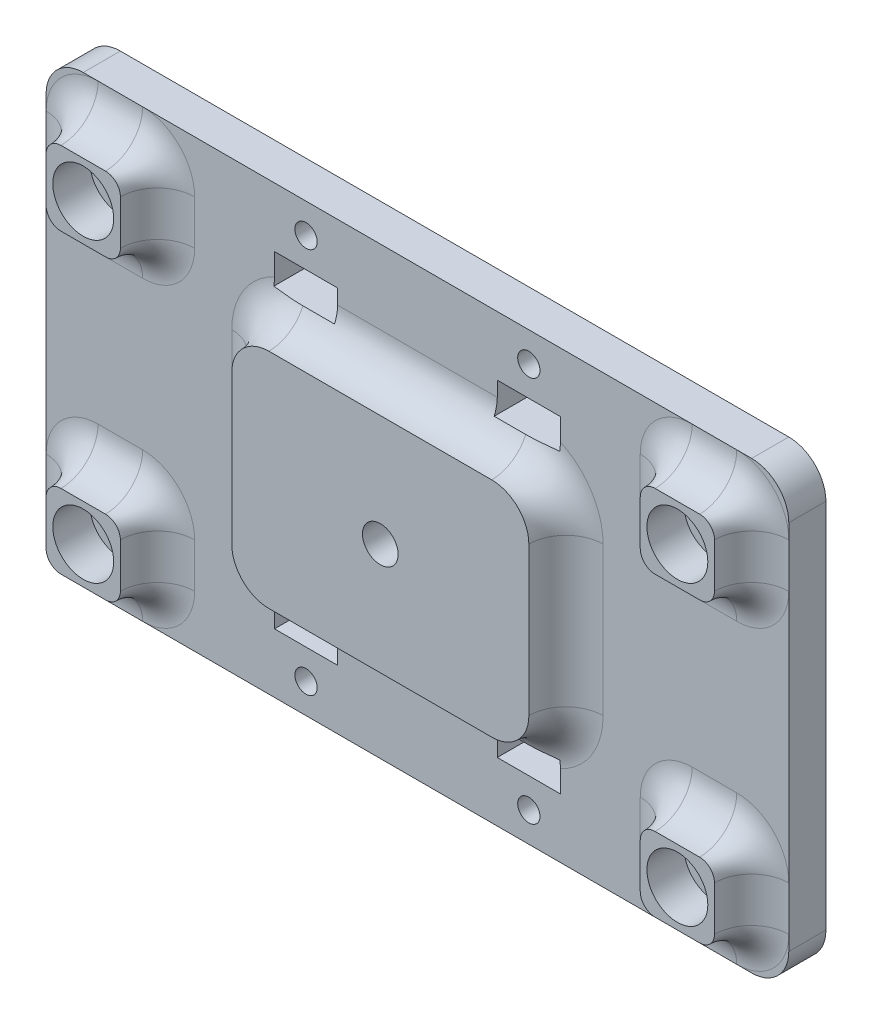
SolidWorks part; units mm, degrees
ref_plane "Front Plane" through (0, 0, 0) normal (0, 0, 1) x (1, 0, 0)
ref_plane "Top Plane" through (0, 0, 0) normal (0, 1, 0) x (1, 0, 0)
ref_plane "Right Plane" through (0, 0, 0) normal (1, 0, 0) x (0, 0, -1)
sketch "Sketch1" plane through (0, 0, 0) normal (0, 0, 1) x (1, 0, 0)
  line L1 (-45, -30) -> (45, -30)
  line L2 (-50, -25) -> (-50, 25)
  line L3 (-45, 30) -> (45, 30)
  line L4 (50, -25) -> (50, 25)
  circle A0 centre (-40, 20) radius 2.25
  circle A1 centre (40, 20) radius 2.25
  circle A2 centre (40, -20) radius 2.25
  circle A3 centre (-40, -20) radius 2.25
  circle A4 centre (0, 0) radius 5
  arc A5 (50, 25) -> (45, 30) centre (45, 25) ccw
  arc A6 (50, -25) -> (45, -30) centre (45, -25) cw
  arc A7 (-45, -30) -> (-50, -25) centre (-45, -25) cw
  arc A8 (-50, 25) -> (-45, 30) centre (-45, 25) cw
  point P0 (0, 0)
  point P6 (0, 0)
  dimension "D1" = 5
  dimension "D3" = 80
  dimension "D4" = 40
extrude "Boss-Extrude1" add sketch "Sketch1" along normal blind 5
sketch "Sketch2" plane through (0, 0, 5) normal (0, 0, 1) x (1, 0, 0)
  line L5 (10.75, -18) -> (19.25, -18)
  line L6 (10.75, -22) -> (10.75, -18)
  line L7 (19.25, -22) -> (19.25, -18)
  line L8 (-19.25, 20) -> (-19.25, 22)
  line L9 (-19.25, 22) -> (-10.75, 22)
  line L10 (-10.75, 22) -> (-10.75, 20)
  line L11 (-10.75, 20) -> (-10.75, 18)
  line L12 (-10.75, 18) -> (-19.25, 18)
  line L13 (-19.25, 18) -> (-19.25, 20)
  line L14 (10.75, 22) -> (19.25, 22)
  line L15 (19.25, 22) -> (19.25, 18)
  line L16 (10.75, 22) -> (10.75, 18)
  line L17 (10.75, 18) -> (19.25, 18)
  line L18 (10.75, -22) -> (19.25, -22)
  line L19 (-19.25, -18) -> (-19.25, -20)
  line L20 (-10.75, -18) -> (-19.25, -18)
  line L21 (-10.75, -20) -> (-10.75, -18)
  line L22 (-10.75, -22) -> (-10.75, -20)
  line L23 (-19.25, -22) -> (-10.75, -22)
  line L24 (-19.25, -20) -> (-19.25, -22)
extrude "Cut-Extrude1" cut sketch "Sketch2" against normal blind 5
sketch "Sketch3" plane through (0, 0, 5) normal (0, 0, 1) x (1, 0, 0)
  line L1 (-43, 15) -> (-37, 15)
  line L2 (-45, 17) -> (-45, 23)
  line L3 (-43, 25) -> (-37, 25)
  line L4 (-35, 17) -> (-35, 23)
  line L7 (43, -15) -> (37, -15)
  line L26 (35, 17) -> (35, 23)
  line L27 (43, 25) -> (37, 25)
  line L28 (45, 17) -> (45, 23)
  line L29 (43, 15) -> (37, 15)
  line L30 (45, -17) -> (45, -23)
  line L31 (43, -25) -> (37, -25)
  line L32 (35, -17) -> (35, -23)
  line L33 (-35, -17) -> (-35, -23)
  line L34 (-43, -25) -> (-37, -25)
  line L35 (-45, -17) -> (-45, -23)
  line L36 (-43, -15) -> (-37, -15)
  arc A0 (-35, 23) -> (-37, 25) centre (-37, 23) ccw
  arc A1 (-37, 15) -> (-35, 17) centre (-37, 17) ccw
  arc A2 (-43, 15) -> (-45, 17) centre (-43, 17) cw
  arc A3 (-45, 23) -> (-43, 25) centre (-43, 23) cw
  arc A4 (45, 23) -> (43, 25) centre (43, 23) ccw
  arc A5 (43, 15) -> (45, 17) centre (43, 17) ccw
  arc A6 (37, 15) -> (35, 17) centre (37, 17) cw
  arc A7 (35, 23) -> (37, 25) centre (37, 23) cw
  arc A8 (35, -23) -> (37, -25) centre (37, -23) ccw
  arc A9 (37, -15) -> (35, -17) centre (37, -17) ccw
  arc A10 (43, -15) -> (45, -17) centre (43, -17) cw
  arc A11 (45, -23) -> (43, -25) centre (43, -23) cw
  arc A12 (-45, -23) -> (-43, -25) centre (-43, -23) ccw
  arc A13 (-43, -15) -> (-45, -17) centre (-43, -17) ccw
  arc A14 (-37, -15) -> (-35, -17) centre (-37, -17) cw
  arc A15 (-35, -23) -> (-37, -25) centre (-37, -23) cw
  point P0 (-40, 20)
  point P8 (0, 0)
  point P16 (0, 0)
  point P29 (0, 0)
  point P41 (40, 20)
  point P60 (40, -20)
  point P61 (-40, -20)
extrude "Boss-Extrude2" add sketch "Sketch3" along normal blind 5
sketch "Sketch4" plane through (0, 0, 10) normal (0, 0, 1) x (1, 0, 0)
  circle A0 centre (-40, 20) radius 4.1
  circle A1 centre (40, 20) radius 4.1
  circle A2 centre (40, -20) radius 4.1
  circle A3 centre (-40, -20) radius 4.1
extrude "Cut-Extrude2" cut sketch "Sketch4" against normal up to surface (5 mm away) up to face at (-37.75, 20, 5)
sketch "Sketch5" plane through (0, 0, 5) normal (0, 0, 1) x (1, 0, 0)
  line L1 (-15, -15) -> (15, -15)
  line L2 (-20, -10) -> (-20, 10)
  line L3 (-15, 15) -> (15, 15)
  line L4 (20, -10) -> (20, 10)
  arc A0 (20, 10) -> (15, 15) centre (15, 10) ccw
  arc A1 (20, -10) -> (15, -15) centre (15, -10) cw
  arc A2 (-15, -15) -> (-20, -10) centre (-15, -10) cw
  arc A3 (-20, 10) -> (-15, 15) centre (-15, 10) cw
  point P0 (0, 0)
  dimension "D1" = 5
extrude "Boss-Extrude3" add sketch "Sketch5" along normal blind 5
sketch "Sketch6" plane through (0, 0, 10) normal (0, 0, 1) x (1, 0, 0)
  circle A0 centre (0, 0) radius 2.4
extrude "Cut-Extrude3" cut sketch "Sketch6" against normal up to surface (5 mm away) up to face at (5, 0, 5)
fillet "Fillet1" radius 5 40 edges at (35.5858, 15.5858, 5) (35, 20, 5) (35.5858, 24.4142, 5) (40, 25, 5) (44.4142, 24.4142, 5) (45, 20, 5) (44.4142, 15.5858, 5) (35.5858, -24.4142, 5) (35, -20, 5) (35.5858, -15.5858, 5) (40, -15, 5) (44.4142, -15.5858, 5) (45, -20, 5) (44.4142, -24.4142, 5) (-44.4142, -24.4142, 5) (-45, -20, 5) (-44.4142, -15.5858, 5) (-40, -15, 5) (-35.5858, -15.5858, 5) (-35, -20, 5) (-35.5858, -24.4142, 5) (-44.4142, 15.5858, 5) (-45, 20, 5) (-44.4142, 24.4142, 5) (-40, 25, 5) (-35.5858, 24.4142, 5) (-35, 20, 5) (-35.5858, 15.5858, 5) (-18.5355, 13.5355, 5) (0, 15, 5) (18.5355, 13.5355, 5) (20, 0, 5) (18.5355, -13.5355, 5) (0, -15, 5) (-18.5355, -13.5355, 5) (40, 15, 5) (40, -25, 5) (-40, -25, 5) (-40, 15, 5) (-20, 0, 5)
sketch "Sketch8" plane through (0, 0, 5) normal (0, 0, 1) x (1, 0, 0)
  circle A0 centre (15, 26) radius 1.5
  circle A1 centre (15, -26) radius 1.5
  circle A2 centre (-15, -26) radius 1.5
  circle A3 centre (-15, 26) radius 1.5
extrude "Cut-Extrude4" cut sketch "Sketch8" against normal up to surface (5 mm away) up to face at (15, 20, 0)
